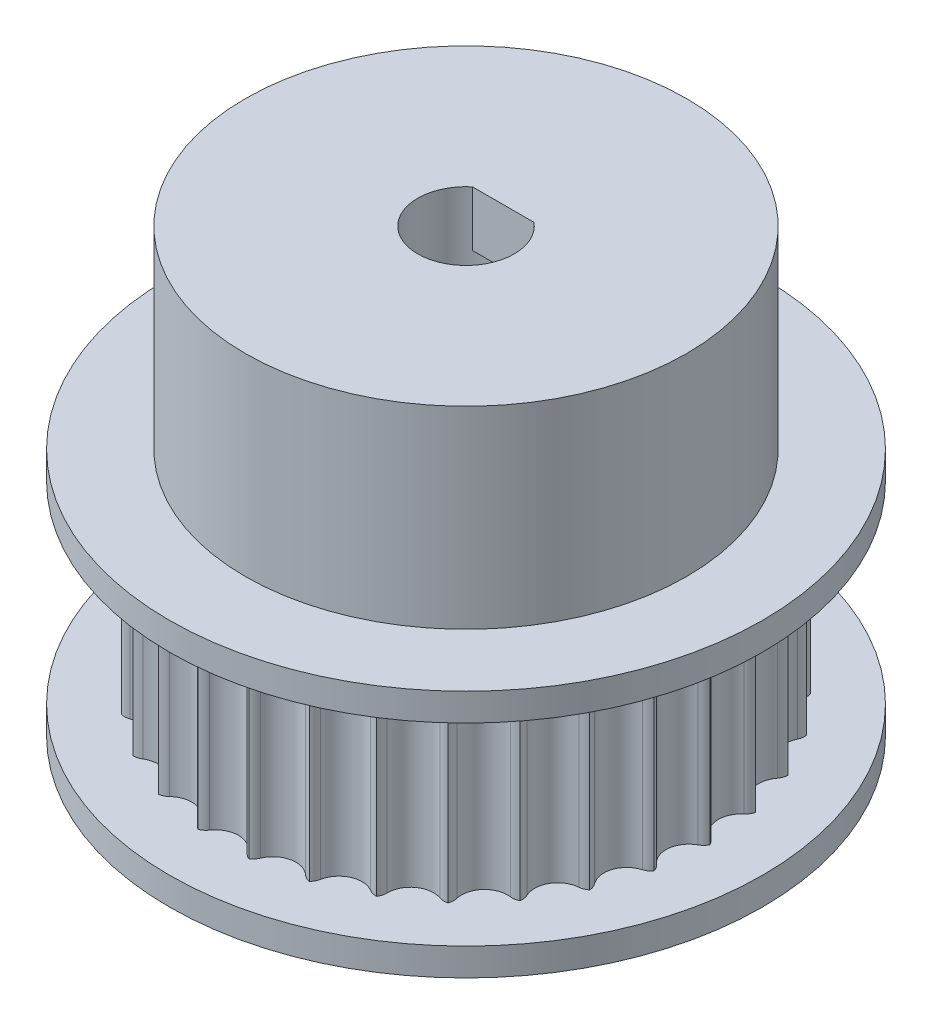
SolidWorks part; units mm, degrees
ref_plane "Front plan" through (0, 0, 0) normal (0, 0, 1) x (1, 0, 0)
ref_plane "Top plan" through (0, 0, 0) normal (0, 1, 0) x (1, 0, 0)
ref_plane "Right plan" through (0, 0, 0) normal (1, 0, 0) x (0, 0, -1)
sketch "Skica2" plane through (0, 0, 0) normal (0, 0, 1) x (1, 0, 0)
  line L0 (8, 8.5) -> (1.75, 8.5)
  line L1 (1.75, 8.5) -> (1.75, -8.5)
  line L2 (1.75, -8.5) -> (6.11, -8.5)
  line L3 (0, -8.5) -> (0, 8.5) construction
  line L4 (0, 8.5) -> (1.75, 8.5)
  line L5 (0, -8.5) -> (1.75, -8.5)
  line L6 (6.11, -8.5) -> (6.11, -7.5)
  line L7 (10.75, 0.5) -> (9.25, 0.5)
  line L8 (9.25, 0.5) -> (9.25, -6.5)
  line L9 (10.75, 0.5) -> (10.75, 1.5)
  line L12 (10.75, -7.5) -> (6.11, -7.5)
  line L13 (10.75, 1.5) -> (8, 1.5)
  line L14 (10.75, -7.5) -> (10.75, -6.5)
  line L15 (9.25, -6.5) -> (10.75, -6.5)
  line L16 (8, 1.5) -> (8, 8.5)
  point P6 (8.43, -7.5)
  point P7 (0, 0)
  dimension "D3" = 18.5
  dimension "D1" = 3.5
  dimension "D2" = 1
  dimension "D4" = 1
  dimension "D6" = 21.5
  dimension "D7" = 16
  dimension "D8" = 17
  dimension "D9" = 7
revolve "Revolute" add sketch "Skica2" angle 360 about L3 region at (5.3256, -0.2329, 0)
sketch "Sketch2" plane through (0, 0.5, 0) normal (0, -1, 0) x (1, 0, 0)
  line L0 (0, 0) -> (0, 9.0829) construction
  line L1 (0, 0) -> (3.0348, 8.4729) construction
  line L3 (0, 0) -> (-1.6132, 8.7491) construction
  circle A1 centre (0, 0) radius 8.2469 construction
  circle A2 centre (0, 0) radius 8.6357 construction
  arc A3 (-0.6881, 8.6082) -> (0.6881, 8.6082) centre (0, 9.0829) ccw
  arc A7 (-1.1652, 8.82) -> (-1.6132, 8.7491) centre (0, 0) ccw
  arc A8 (0, 10.1685) -> (1.6132, 8.7491) centre (0.3953, 8.9913) cw
  circle A9 centre (0, 0) radius 9 construction
  arc A10 (1.1652, 8.82) -> (1.6132, 8.7491) centre (0, 0) cw
  arc A11 (1.1652, 8.82) -> (0.6881, 8.6082) centre (1.0997, 8.3243) ccw
  arc A12 (0, 10.1685) -> (-1.6132, 8.7491) centre (-0.3953, 8.9913) ccw
  arc A13 (-1.1652, 8.82) -> (-0.6881, 8.6082) centre (-1.0997, 8.3243) cw
  circle M8 centre (0, 0) radius 9.25
  dimension "D2" = 1
  dimension "D3" = 1.2417
  dimension "D4" = 0.836
  dimension "D6" = 18
extrude "Cut-Extrude1" cut sketch "Sketch2" along normal up to surface (7 mm away) contours A8 M8 | A11 A3 M8 region at (0, 0.5, 8.8612) region at (0, 0.5, 9.6545) up to face at (10.75, -6.5, 0)
pattern_circular "CirPattern1" count 30 over 360 about axis through (0, -8.5, 0) along (0, -1, 0) of "Cut-Extrude1" reverse direction yes
sketch "Sketch3" plane through (0, 0, 0) normal (1, 0, 0) x (0, 0, -1)
  line L0 (0, 8.5) -> (0, 0.5) construction
  line L1 (1.75, 8.5) -> (-1.75, 8.5) construction
  circle A0 centre (0, 4.5) radius 1.65
  dimension "D1" = 3.3
extrude "Cut-Extrude2" cut sketch "Sketch3" against normal up to next
sketch "Sketch4" plane through (0, 0, 0) normal (0, 0, 1) x (1, 0, 0)
  line L0 (0, 8.5) -> (0, 0.5) construction
  line L1 (10.75, 8.5) -> (-10.75, 8.5) construction
  line L2 (-0.6881, 0.5) -> (0.6881, 0.5) construction
  circle A0 centre (0, 4.5) radius 1.65
  dimension "D1" = 3.3
extrude "Cut-Extrude3" cut sketch "Sketch4" against normal up to next
chamfer "Chamfer1" distance 1 angle 45 1 edges at (6.11, -7.5, 0)
sketch "Sketch6" plane through (0, 8.5, 0) normal (0, 1, 0) x (1, 0, 0)
  line L1 (-1.1136, 1.35) -> (1.1136, 1.35)
  arc A0 (1.1136, 1.35) -> (-1.1136, 1.35) centre (0, 0) ccw
  circle A1 centre (0, 0) radius 1.75 construction
  point P3 (0, 0)
  point P4 (0, 0)
  point P6 (0, 1.75)
  point P7 (0, 0)
  point P8 (0, 0)
  point P9 (-1.1227, 1.3424)
  dimension "D1" = 0.4
extrude "Boss-Extrude1" add sketch "Sketch6" against normal blind 2
equation "\"`\"=2"
